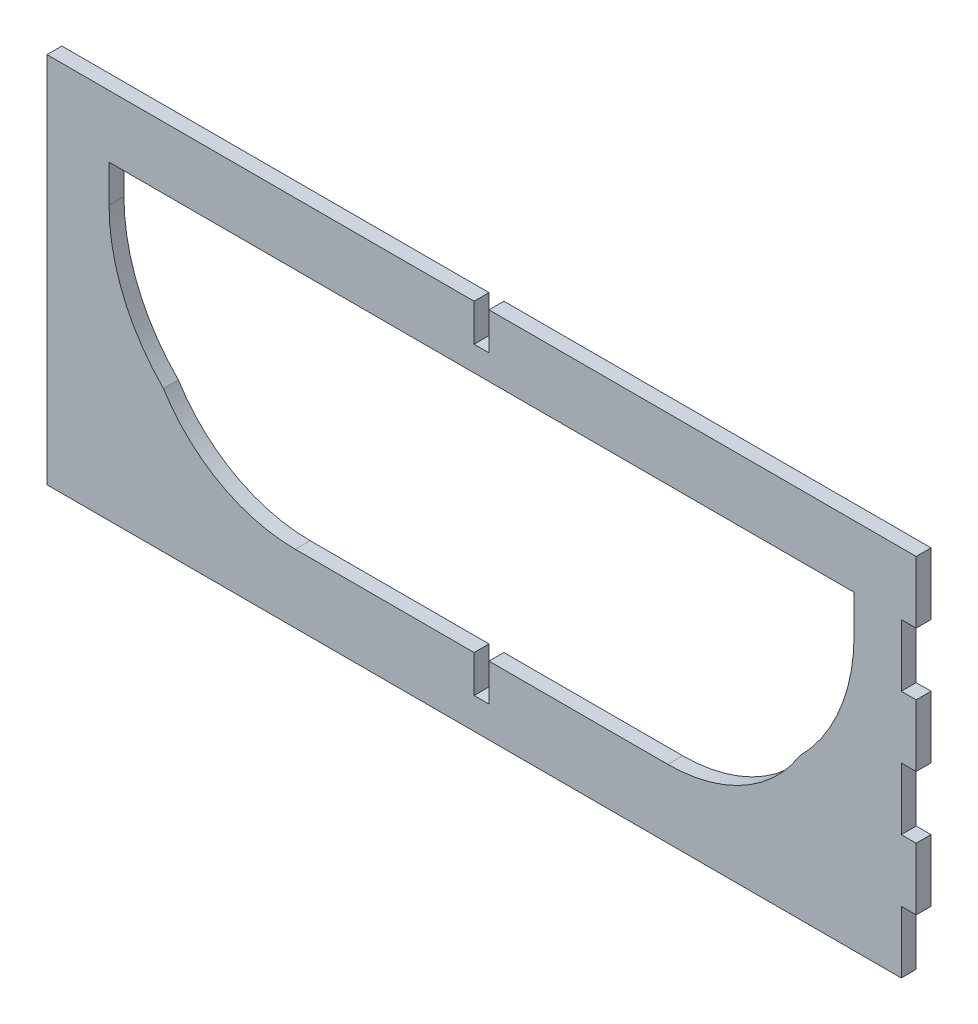
SolidWorks part; units mm, degrees
ref_plane "Front" through (0, 0, 0) normal (0, 0, 1) x (1, 0, 0)
ref_plane "Top" through (0, 0, 0) normal (0, 1, 0) x (1, 0, 0)
ref_plane "Right" through (0, 0, 0) normal (1, 0, 0) x (0, 0, -1)
sketch "Sketch1" plane through (0, 0, 0) normal (0, 0, 1) x (1, 0, 0)
  line L1 (0, 0) -> (-200, 0)
  line L2 (0, 0) -> (0, 150)
  line L4 (-200, 0) -> (-200, 150)
  line L5 (-100, 90) -> (-100, 0) construction
  line L6 (-175, 110) -> (-175, 125)
  line L7 (-25, 110) -> (-25, 125)
  line L9 (-175, 125) -> (-25, 125)
  line L11 (-200, 150) -> (0, 150)
  arc A0 (-153.0972, 57.0313) -> (-46.9028, 57.0312) centre (-100, 90) ccw
  arc A1 (-175, 110) -> (-153.0972, 57.0313) centre (-100, 110) ccw
  arc A2 (-46.9028, 57.0312) -> (-25, 110) centre (-100, 110) ccw
  point P6 (0, 0)
  point P16 (0, 0)
  point P17 (0, 0)
  dimension "D3" = 62.5
  dimension "D4" = 75
  dimension "D1" = 200
  dimension "D2" = 25
  dimension "D5" = 20
  dimension "D6" = 90
  dimension "D7" = 150
extrude "Boss-Extrude1" add sketch "Sketch1" along normal blind 6
sketch "Sketch3" plane through (0, 0, 6) normal (0, 0, 1) x (1, 0, 0)
  line L0 (-200, 150) -> (-200, 0) construction
  line L1 (-100, 27.5) -> (-200, 27.5)
  line L2 (-100, 27.5) -> (-100, 125)
  line L3 (-100, 125) -> (-200, 125)
  line L4 (-200, 27.5) -> (-200, 125)
  line L7 (-25, 125) -> (-175, 125) construction
  arc A0 (-153.0972, 57.0313) -> (-46.9028, 57.0312) centre (-100, 90) ccw construction
extrude "Cut-Extrude1" cut sketch "Sketch3" against normal blind 6
sketch "Sketch4" plane through (0, 0, 6) normal (0, 0, 1) x (1, 0, 0)
  line L0 (-250, 110) -> (-100, 110) construction
  line L1 (-100, 90) -> (-250, 90) construction
  line L2 (-250, 90) -> (-250, 110) construction
  line L3 (-25, 125) -> (0, 125) construction
  line L4 (-200, 27.5) -> (-250, 27.5)
  line L5 (-200, 27.5) -> (-200, 0)
  line L6 (-200, 0) -> (-350, 0)
  line L9 (-350, 0) -> (-350, 150)
  line L11 (-325, 110) -> (-325, 125)
  line L12 (-200, 125) -> (-325, 125)
  line L13 (-200, 125) -> (-200, 150)
  line L14 (-200, 150) -> (-350, 150)
  line L16 (0, 0) -> (0, 150) construction
  line L17 (-325, 125) -> (-350, 125) construction
  line L18 (-200, 0) -> (0, 0) construction
  arc A0 (-325, 110) -> (-303.0972, 57.0312) centre (-250, 110) ccw
  circle A1 centre (-100, 90) radius 62.5 construction
  circle A2 centre (-100, 110) radius 75 construction
  arc A3 (-46.9028, 57.0312) -> (-25, 110) centre (-100, 110) ccw construction
  arc A4 (-100, 27.5) -> (-46.9028, 57.0312) centre (-100, 90) ccw construction
  arc A5 (-303.0972, 57.0312) -> (-250, 27.5) centre (-250, 90) ccw
  point P20 (-350, 1.6583)
  point P36 (-200, 125)
  point P38 (-200, 150)
  point P40 (-25, 125)
  point P42 (0, 0)
  point P43 (0, 0)
  dimension "D1" = 150
  dimension "D2" = 125
  dimension "D4" = 125
  dimension "D3" = 150
extrude "Boss-Extrude3" add sketch "Sketch4" against normal blind 6
sketch "Sketch5" plane through (0, 0, 6) normal (0, 0, 1) x (1, 0, 0)
  line L1 (-178, 150) -> (-172, 150)
  line L2 (-178, 150) -> (-178, 135)
  line L3 (-178, 135) -> (-172, 135)
  line L4 (-172, 150) -> (-172, 135)
  line L5 (-250, 27.5) -> (-100, 27.5) construction
  line L6 (-178, 27.5) -> (-172, 27.5)
  line L7 (-178, 27.5) -> (-178, 12.5)
  line L8 (-178, 12.5) -> (-172, 12.5)
  line L9 (-172, 27.5) -> (-172, 12.5)
  line L10 (0, 150) -> (-350, 150) construction
  point P4 (-177.5407, 147.9373)
  point P12 (-175, 150)
  point P14 (-175, 150)
  dimension "D1" = 6
  dimension "D2" = 15
extrude "Cut-Extrude2" cut sketch "Sketch5" against normal blind 6
sketch "Sketch6" plane through (0, 0, 6) normal (0, 0, 1) x (1, 0, 0)
  line L0 (0, 0) -> (0, 150) construction
  line L1 (0, 125) -> (-6, 125)
  line L2 (0, 125) -> (0, 100)
  line L3 (0, 100) -> (-6, 100)
  line L4 (-6, 125) -> (-6, 100)
  line L5 (0, 150) -> (-172, 150) construction
  dimension "D1" = 25
  dimension "6" = 6
  dimension "D2" = 25
extrude "Cut-Extrude3" cut sketch "Sketch6" against normal blind 6
pattern_linear "LPattern1" count 3 spacing 50 along (0, -1, 0) of "Cut-Extrude3"
